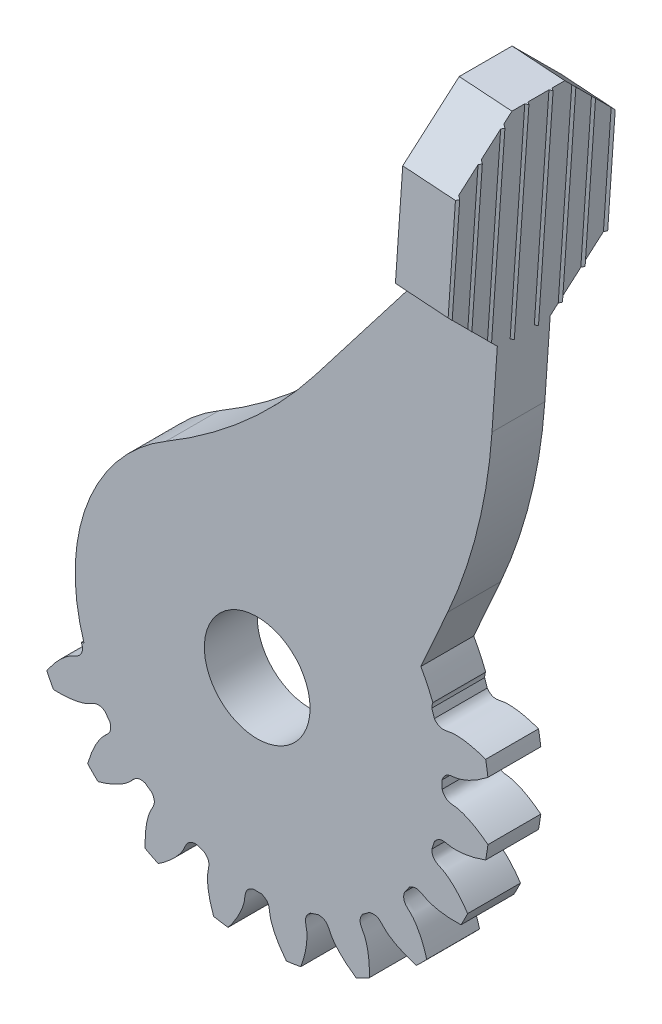
SolidWorks part; units mm, degrees
ref_plane "前视基准面" through (0, 0, 0) normal (0, 0, 1) x (1, 0, 0)
ref_plane "上视基准面" through (0, 0, 0) normal (0, 1, 0) x (1, 0, 0)
ref_plane "右视基准面" through (0, 0, 0) normal (1, 0, 0) x (0, 0, -1)
other "Configuration Table"
sketch "草图1" plane through (0, 0, 0) normal (0, 0, 1) x (1, 0, 0)
  circle A0 centre (0, 0) radius 22
extrude "凸台-拉伸1" add sketch "草图1" along normal blind 30
ref_axis "基准轴1" through (0, 0, 30) along (0, 0, -1)
sketch "草图2" plane through (0, 0, 0) normal (0, 0, 1) x (1, 0, 0)
  line L0 (0, 0) -> (0, 22) construction
  circle A0 centre (0, 0) radius 22 construction
  arc A1 (0.3866, 17.4957) -> (-0.3866, 17.4957) centre (0, 0) ccw
  arc A2 (6.3623, 24.9965) -> (-6.3623, 24.9965) centre (0, 0) ccw
  spline S0 degree 3 poles (0.3866, 17.4957) (1.2224, 17.787) (1.1142, 18.3742) (1.2258, 18.94) (1.2378, 18.9951) (1.2526, 19.0573) (1.2706, 19.1264) (1.292, 19.2024) (1.317, 19.2851) (1.3461, 19.3745) (1.3793, 19.4704) (1.4171, 19.5726) (1.4597, 19.6811) (1.5073, 19.7956) (1.5603, 19.9161) (1.6187, 20.0423) (1.683, 20.174) (1.7534, 20.3112) (1.83, 20.4535) (1.9132, 20.6008) (2.0031, 20.7529) (2.1, 20.9095) (2.204, 21.0705) (2.3155, 21.2356) (2.4346, 21.4046) (2.5615, 21.5772) (2.6964, 21.7533) (2.8395, 21.9324) (2.991, 22.1145) (3.1509, 22.2992) (3.3196, 22.4862) (3.4971, 22.6753) (3.6837, 22.8662) (3.8793, 23.0586) (4.0843, 23.2521) (4.2986, 23.4467) (4.5225, 23.6418) (4.7559, 23.8372) (4.9991, 24.0327) (5.2521, 24.2278) (5.515, 24.4223) (5.8829, 24.6833) (6.1679, 24.8727) (6.3623, 24.9965) knots 0 0 0 0 0.165916 0.170906 0.176664 0.183189 0.190482 0.198542 0.207371 0.216967 0.22733 0.238462 0.250361 0.263027 0.276462 0.290664 0.305634 0.321371 0.337876 0.355149 0.37319 0.391998 0.411574 0.431917 0.453028 0.474907 0.497554 0.520968 0.54515 0.570099 0.595817 0.622302 0.649554 0.677575 0.706363 0.735918 0.766242 0.797333 0.829191 0.861818 0.895212 0.929373 1 1 1 1
  spline S1 degree 3 poles (-0.3866, 17.4957) (-1.2224, 17.787) (-1.1142, 18.3742) (-1.2258, 18.94) (-1.2378, 18.9951) (-1.2526, 19.0573) (-1.2706, 19.1264) (-1.292, 19.2024) (-1.317, 19.2851) (-1.3461, 19.3745) (-1.3793, 19.4704) (-1.4171, 19.5726) (-1.4597, 19.6811) (-1.5073, 19.7956) (-1.5603, 19.9161) (-1.6187, 20.0423) (-1.683, 20.174) (-1.7534, 20.3112) (-1.83, 20.4535) (-1.9132, 20.6008) (-2.0031, 20.7529) (-2.1, 20.9095) (-2.204, 21.0705) (-2.3155, 21.2356) (-2.4346, 21.4046) (-2.5615, 21.5772) (-2.6964, 21.7533) (-2.8395, 21.9324) (-2.991, 22.1145) (-3.1509, 22.2992) (-3.3196, 22.4862) (-3.4971, 22.6753) (-3.6837, 22.8662) (-3.8793, 23.0586) (-4.0843, 23.2521) (-4.2986, 23.4467) (-4.5225, 23.6418) (-4.7559, 23.8372) (-4.9991, 24.0327) (-5.2521, 24.2278) (-5.515, 24.4223) (-5.8829, 24.6833) (-6.1679, 24.8727) (-6.3623, 24.9965) knots 0 0 0 0 0.165916 0.170906 0.176664 0.183189 0.190482 0.198542 0.207371 0.216967 0.22733 0.238462 0.250361 0.263027 0.276462 0.290664 0.305634 0.321371 0.337876 0.355149 0.37319 0.391998 0.411574 0.431917 0.453028 0.474907 0.497554 0.520968 0.54515 0.570099 0.595817 0.622302 0.649554 0.677575 0.706363 0.735918 0.766242 0.797333 0.829191 0.861818 0.895212 0.929373 1 1 1 1
extrude "切除-拉伸1" cut sketch "草图2" along normal through all
pattern_circular "阵列(圆周)1" count 20 every 18 about axis through (0, 0, 30) along (0, 0, -1) of "切除-拉伸1"
sketch "草图3" plane through (0, 0, 0) normal (0, 0, 1) x (1, 0, 0)
  circle A0 centre (0, 0) radius 20 construction
  dimension "Dn" = 40
sketch "草图4" plane through (0, 0, 30) normal (0, 0, 1) x (1, 0, 0)
  circle A0 centre (0, 0) radius 42.426
extrude "切除-拉伸2" cut sketch "草图4" against normal blind 25
sketch "草图5" plane through (0, 0, 5) normal (0, 0, 1) x (1, 0, 0)
  circle A0 centre (0, 0) radius 5
  dimension "D1" = 10
extrude "切除-拉伸3" cut sketch "草图5" against normal blind 30
sketch "草图6" plane through (0, 0, 5) normal (0, 0, 1) x (1, 0, 0)
  line L0 (21.4732, 49.6209) -> (21.4732, 71.5419)
  line L2 (21.4732, 49.6209) -> (14.4798, 49.6209)
  line L3 (14.4798, 49.6209) -> (14.4798, 39.9321)
  line L6 (16.8895, 5.5023) -> (23.9182, 7.7922)
  line L8 (-16.3886, -5.3391) -> (-23.4173, -7.629)
  arc A0 (16.8895, 5.5023) -> (-16.3886, -5.3391) centre (0.2771, 0) ccw
  arc A1 (23.9182, 7.7922) -> (-23.4173, -7.629) centre (0.2771, 0) ccw
  point P19 (20.7328, 6.7544)
  dimension "D1" = 35
extrude "切除-拉伸6" cut sketch "草图6" against normal through all both and the other way through all contours L6 A1 L8 A0 region at (-5.3247, 17.1947, 5)
sketch "草图7" plane through (0, 0, 5) normal (0, 0, 1) x (1, 0, 0)
  line L1 (21.6029, 22.439) -> (22.2943, 32.4151)
  line L2 (22.2943, 32.4151) -> (19.3014, 32.6225)
  line L3 (19.3014, 32.6225) -> (18.6101, 22.6464)
  line L4 (18.6101, 22.6464) -> (5.6459, 11.3626)
  line L5 (10, -0.693) -> (21.6029, 22.439)
  line L6 (18.6101, 22.6464) -> (25.9302, 22.1392) construction
  line L7 (10, -0.693) -> (5.6459, 11.3626)
  dimension "D2" = 10
  dimension "D3" = 3
extrude "凸台-拉伸2" add sketch "草图7" against normal up to surface (5 mm away) up to face at (5, 0, 0)
sketch "草图8" plane through (0, 0, 5) normal (0, 0, 1) x (1, 0, 0)
  line L5 (21.6029, 22.439) -> (24.1001, 58.4738)
  line L6 (15.3581, 8.3892) -> (21.6029, 22.439)
  line L7 (-4.4162, 14.7069) -> (15.3581, 8.3892)
  line L8 (18.0751, 43.8554) -> (-4.4162, 14.7069)
  line L9 (19.112, 58.8195) -> (18.0751, 43.8554)
  line L10 (19.112, 58.8195) -> (24.1001, 58.4738)
extrude "凸台-拉伸3" add sketch "草图8" against normal up to surface (5 mm away) up to face at (4.7318, -3.3528, 0)
ref_plane "基准面1" through (0, 0, 2.5) normal (0, 0, 1) x (1, 0, 0)
sketch "草图9" plane through (0, 0, 2.5) normal (0, 0, 1) x (1, 0, 0)
  line L0 (19.112, 58.8195) -> (24.1001, 58.4738)
  line L1 (18.0751, 43.8554) -> (23.0631, 43.5097)
  line L2 (21.6029, 22.439) -> (24.1001, 58.4738) construction
  line L3 (23.0631, 43.5097) -> (24.1001, 58.4738)
  line L4 (19.112, 58.8195) -> (18.0751, 43.8554)
extrude "凸台-拉伸4" add sketch "草图9" along normal mid plane 15
chamfer "倒角1" distance 5 angle 45 4 edges at (20.5691, 43.6825, 0) (20.5691, 43.6825, 5) (21.6061, 58.6466, -5) (21.6061, 58.6466, 10)
fillet "圆角1" radius 50 2 edges at (-2.4227, 17.2905, 2.5) (21.6029, 22.439, 2.5)
sketch "草图10" plane through (4.1479, 59.8565, 0) normal (0.0691, 0.9976, 0) x (0.9976, -0.0691, 0)
  line L0 (20, 5) -> (20.25, 4.8557)
  line L1 (20.25, 4.8557) -> (20, 4.7113)
  line L2 (20, 5) -> (20, 0) construction
  line L4 (20, 3) -> (20.25, 2.8557)
  line L5 (20.25, 2.8557) -> (20, 2.7113)
  line L7 (20, 1) -> (20.25, 0.8557)
  line L8 (20.25, 0.8557) -> (20, 0.7113)
  line L10 (20, -1.2113) -> (20.25, -1.3557)
  line L11 (20.25, -1.3557) -> (20, -1.5)
  line L12 (20, 0) -> (20, -5) construction
  line L14 (20, -3.5) -> (20.25, -3.6443)
  line L15 (20.25, -3.6443) -> (20, -3.7887)
  line L17 (20, -5) -> (20, -10) construction
  line L18 (20, -5.7113) -> (20.25, -5.8557)
  line L19 (20.25, -5.8557) -> (20, -6)
  line L21 (20, -7.7113) -> (20.25, -7.8557)
  line L22 (20.25, -7.8557) -> (20, -8)
  line L24 (20, -9.7113) -> (20.25, -9.8557)
  line L25 (20.25, -9.8557) -> (20, -10)
  line L32 (16.3705, -5) -> (21.2731, -5) construction
  line L33 (21.2731, 0) -> (16.3705, 0) construction
  line L34 (20, 1) -> (20.25, 0.8557)
  line L35 (20, 5) -> (20, 4.7113)
  line L36 (20, -9.7113) -> (20, -10)
  line L37 (20, -7.7113) -> (20, -8)
  line L38 (20, -5.7113) -> (20, -6)
  line L39 (20, -3.5) -> (20, -3.7887)
  line L40 (20, -1.2113) -> (20, -1.5)
  line L41 (20, 1) -> (20, 0.7113)
  line L42 (20, 3) -> (20, 2.7113)
  line M27 (20, -5) -> (20, 0)
  dimension "D1" = 60
  dimension "D2" = 60
  dimension "D3" = 60
  dimension "D4" = 60
  dimension "D5" = 60
  dimension "D6" = 60
  dimension "D7" = 60
  dimension "D8" = 60
  dimension "D9" = 0.25
  dimension "D11" = 2
  dimension "D12" = 60
  dimension "D14" = 2
  dimension "D15" = 60
  dimension "D17" = 1.5
  dimension "D18" = 60
  dimension "D19" = 60
  dimension "D20" = 0.25
  dimension "D21" = 1.5
  dimension "D22" = 60
  dimension "D23" = 60
  dimension "D24" = 0.25
  dimension "D25" = 2
  dimension "D26" = 60
  dimension "D27" = 0.25
  dimension "D28" = 2
  dimension "D30" = 60
extrude "凸台-拉伸5" add sketch "草图10" against normal blind 30 contours L0 L35 L1 | L4 L42 L5 | L7 L41 L8 | L11 L10 M27 | L15 L14 M27 | L18 L38 L19 | L21 L37 L22 | L24 L36 L25 region at (24.1832, 58.468, -4.8557) region at (24.1832, 58.468, -2.8557) region at (24.1832, 58.468, -0.8557) region at (24.1832, 58.468, 3.6443) region at (24.1832, 58.468, 1.3557) region at (24.1832, 58.468, 5.8557) region at (24.1832, 58.468, 7.8557) region at (24.1832, 58.468, 9.8557)
sketch "草图11" plane through (19.9522, -1.3826, 0) normal (0.9976, -0.0691, 0) x (0, 0, -1)
  line L0 (-5, 60) -> (0, 60)
  line L1 (0, 60) -> (5, 55)
  line L2 (0, 40) -> (5, 45)
  line L3 (5, 55) -> (5, 45)
  line L6 (0, 40) -> (-5, 40)
  line L7 (-5, 40) -> (-10, 45)
  line L8 (-10, 45) -> (-10, 55)
  line L10 (-20.7205, 21.3549) -> (15.6127, 21.3549)
  line L11 (-5, 60) -> (-10, 55)
  line L12 (-20.7205, 21.3549) -> (-20.7205, -21.0158)
  line L13 (-20.7205, -21.0158) -> (15.6127, -21.0158)
  line L14 (15.6127, 21.3549) -> (15.6127, -21.0158)
extrude "切除-拉伸7" cut sketch "草图11" along normal blind 30 flip side to cut
